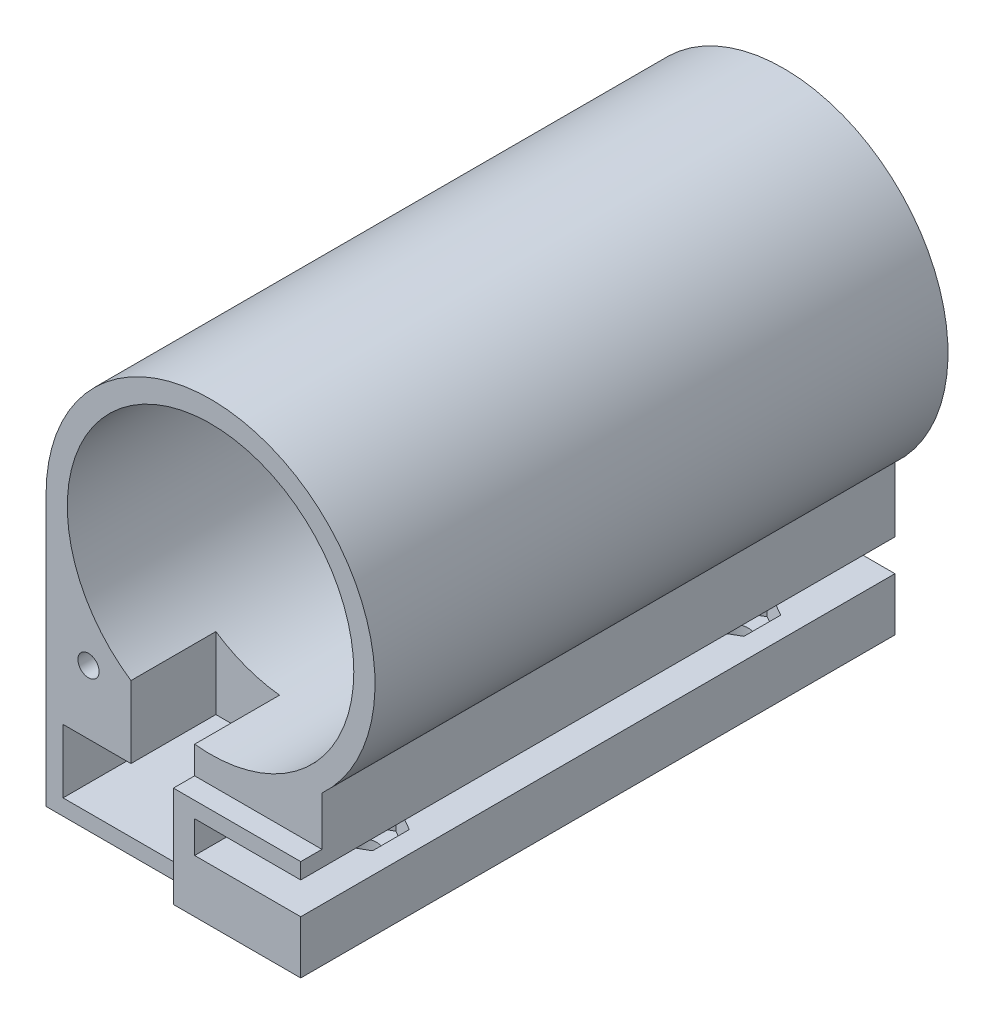
SolidWorks part; units mm, degrees
ref_plane "Plano frontal" through (0, 0, 0) normal (0, 0, 1) x (1, 0, 0)
ref_plane "Plano superior" through (0, 0, 0) normal (0, 1, 0) x (1, 0, 0)
ref_plane "Plano direito" through (0, 0, 0) normal (1, 0, 0) x (0, 0, -1)
sketch "Esboço1" plane through (0, 0, 0) normal (0, 0, 1) x (1, 0, 0)
  line L0 (-0.5, 0) -> (15, 0) construction
  line L2 (-16, 0) -> (-16, -25.5)
  line L3 (-16, -25.5) -> (10, -25.5)
  line L6 (0, -17.5) -> (0, -20.5)
  line L7 (0, -20.5) -> (10, -20.5)
  line L8 (10, -20.5) -> (10, -25.5)
  line L9 (-0.5, 8) -> (-0.5, 11) construction
  line L12 (-2.2, 8) -> (-2.2, 11)
  line L13 (1.2, 8) -> (1.2, 11)
  line L14 (-0.5, -8) -> (-0.5, -11) construction
  line L15 (-2.2, -8) -> (-2.2, -11)
  line L17 (1.2, -8) -> (1.2, -11)
  line L19 (0, -17.5) -> (10, -17.5)
  line L20 (10, -17.5) -> (10, -11.4018)
  line L25 (-14.4, -18) -> (-2, -18)
  line L26 (-14.4, -18) -> (-14.4, -24)
  line L27 (-14.4, -24) -> (-2, -24)
  line L28 (-2, -18) -> (-2, -24)
  line L29 (-14.4, -18) -> (-2, -24) construction
  line L30 (-14.4, -24) -> (-2, -18) construction
  circle A0 centre (-0.5, 0) radius 4.5
  arc A3 (10, -11.4018) -> (-16, 0) centre (-0.5, 0) ccw
  circle A4 centre (-0.5, 0) radius 13.5
  arc A5 (-2.2, 8) -> (1.2, 8) centre (-0.5, 8) ccw
  arc A6 (1.2, 11) -> (-2.2, 11) centre (-0.5, 11) ccw
  arc A7 (-2.2, -8) -> (1.2, -8) centre (-0.5, -8) cw
  arc A8 (1.2, -11) -> (-2.2, -11) centre (-0.5, -11) cw
  arc A9 (-16, 0) -> (10, -11.4018) centre (-0.5, 0) ccw construction
  point P0 (0, 0)
  point P8 (0, 9.4)
  point P11 (-0.5, 9.5)
  point P18 (-8.2, -21)
  point P25 (-0.5, -9.5)
  point P43 (0, -19)
  dimension "D2" = 9
  dimension "D8" = 1.7
  dimension "D9" = 2
  dimension "D11" = 27
  dimension "D17" = 4
  dimension "D3" = 3
  dimension "D4" = 10
  dimension "D5" = 5
  dimension "D6" = 5
  dimension "D7" = 3
  dimension "D10" = 10
  dimension "D12" = 6
  dimension "D13" = 2
  dimension "D14" = 19
  dimension "D15" = 12.4
  dimension "D16" = 1.5
  dimension "D20" = 19
extrude "Ressalto-extrusão1" add sketch "Esboço1" along normal mid plane 56 contours L3 L8 L7 L6 L2 L25 L28 L27 L26 | L28 L25 L26 L27 | A0 region at (5.5185, 13.7243, 0) region at (-8.2, -21, 0) region at (-13.6182, 0, 0)
extrude "Corte-extrusão5" cut sketch "Esboço1<3>" against normal offset from surface (54 mm away) 2 from surface contours L28 L25 L26 L27 | A0 region at (-8.2, -21, 0) region at (-13.6182, 0, 0) up to face at (2.0906, -14.8132, -28) starting at face at (2.0906, -14.8132, 28)
sketch "Esboço1<3>" plane through (0, 0, 0) normal (0, 0, 1) x (1, 0, 0) same geometry as "Esboço1"
sketch "Esboço3" plane through (0, 0, 28) normal (0, 0, 1) x (1, 0, 0)
  line L5 (-8, -11.225) -> (-8, -18)
  line L13 (-8, -18) -> (-2, -18)
  line L14 (-2, -18) -> (-2, -13.4164)
  line L15 (-2, -13.4164) -> (-8, -11.225)
  line L16 (-14.4, -18) -> (-2, -18) construction
  circle A0 centre (-12, -12) radius 1
  circle A2 centre (-0.5, 0) radius 13.5 construction
  dimension "D1" = 2
  dimension "D3" = 11.5
  dimension "D2" = 12
  dimension "D4" = 6
extrude "Corte-extrusão3" cut sketch "Esboço3" against normal blind 10
sketch "Esboço4" plane through (0, 0, 28) normal (0, 0, 1) x (1, 0, 0)
  line L3 (-2, -25.5) -> (-16, -25.5)
  line L4 (-16, -25.5) -> (10, -25.5) construction
  line L7 (-16, -25.5) -> (-16, 0)
  line L8 (10, -11.4018) -> (10, -16)
  line L9 (10, -17.5) -> (10, -11.4018) construction
  line L10 (10, -16) -> (-2, -16)
  line L11 (-2, -24) -> (-2, -13.4164) construction
  line L12 (-2, -16) -> (-2, -25.5)
  line L13 (0, -17.5) -> (10, -17.5) construction
  arc A2 (-16, 0) -> (10, -11.4018) centre (-0.5, 0) cw
  arc A4 (10, -11.4018) -> (-16, 0) centre (-0.5, 0) ccw construction
  dimension "D1" = 1.5
  dimension "D2" = 25.5
extrude "Corte-extrusão4" cut sketch "Esboço4" against normal blind 2
sketch "Esboço5" plane through (0, -20.5, 0) normal (0, 1, 0) x (1, 0, 0)
  line L0 (0, 0) -> (15.9501, 0) construction
  line L1 (5, 14.0359) -> (8, 15.7679)
  line L2 (8, 15.7679) -> (8, 19.2321)
  line L3 (8, 19.2321) -> (5, 20.9641)
  line L4 (5, 20.9641) -> (2, 19.2321)
  line L5 (2, 19.2321) -> (2, 15.7679)
  line L6 (2, 15.7679) -> (5, 14.0359)
  line L7 (5, -20.9641) -> (8, -19.2321)
  line L8 (8, -19.2321) -> (8, -15.7679)
  line L9 (8, -15.7679) -> (5, -14.0359)
  line L10 (5, -14.0359) -> (2, -15.7679)
  line L11 (2, -15.7679) -> (2, -19.2321)
  line L12 (2, -19.2321) -> (5, -20.9641)
  line L13 (0, -28) -> (10, -28) construction
  circle A0 centre (5, 17.5) radius 3 construction
  circle A1 centre (5, -17.5) radius 3 construction
  circle A2 centre (5, -17.5) radius 1.65
  circle A3 centre (5, 17.5) radius 1.65
  point P21 (5, -28)
  dimension "D1" = 6
  dimension "D3" = 3.3
  dimension "D2" = 35
extrude "Corte-extrusão6" cut sketch "Esboço5" against normal blind 2.5
extrude "Corte-extrusão7" cut sketch "Esboço5<2>" against normal through all contours A2 | A3
sketch "Esboço5<2>" plane through (0, -20.5, 0) normal (0, 1, 0) x (1, 0, 0) same geometry as "Esboço5"
sketch "Esboço6" plane through (0, 0, -26) normal (0, 0, 1) x (1, 0, 0)
  line L1 (-14.4, -24) -> (-9.4, -24)
  line L2 (-14.4, -24) -> (-14.4, -21)
  line L3 (-14.4, -21) -> (-9.4, -21)
  line L4 (-9.4, -24) -> (-9.4, -21)
  dimension "D1" = 5
  dimension "D2" = 3
extrude "Corte-extrusão8" cut sketch "Esboço6" against normal through all
